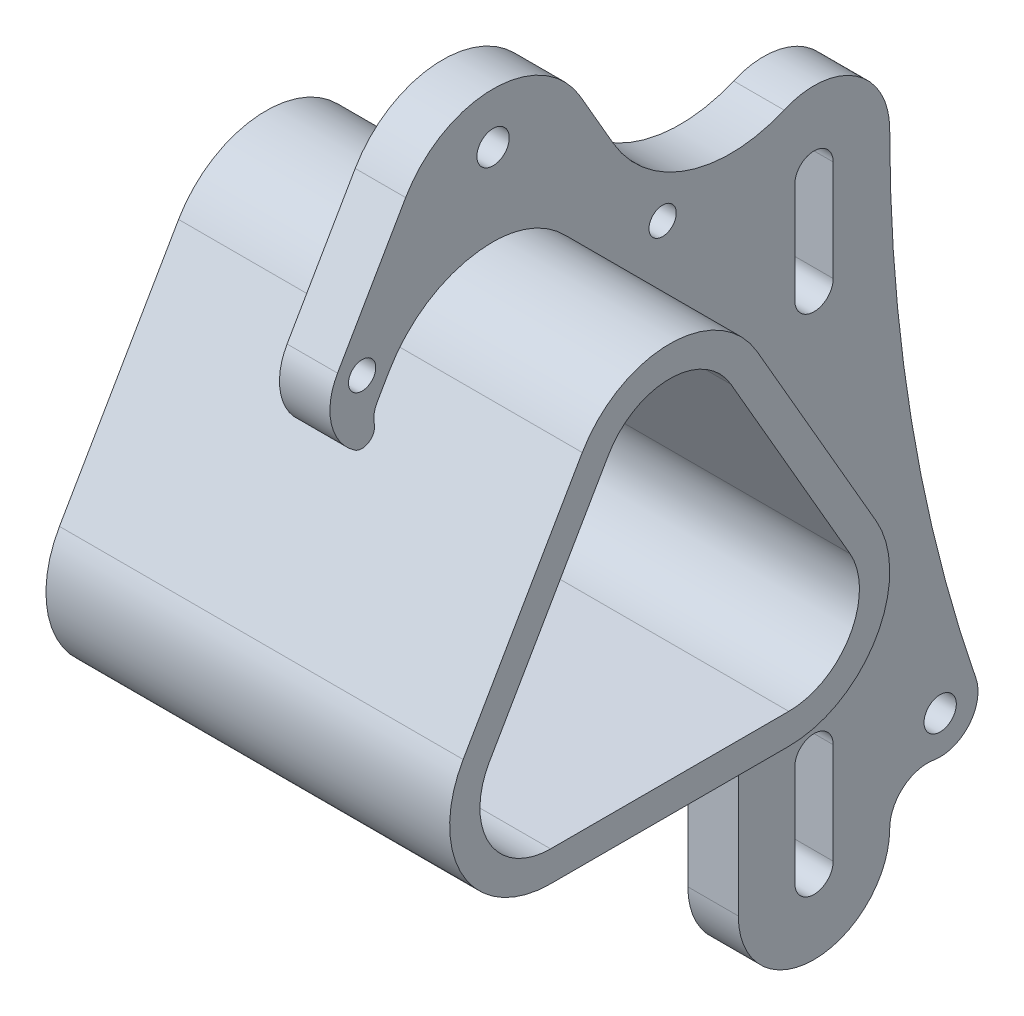
SolidWorks part; units mm, degrees
ref_plane "Front Plane" through (0, 0, 0) normal (0, 0, 1) x (1, 0, 0)
ref_plane "Top Plane" through (0, 0, 0) normal (0, 1, 0) x (1, 0, 0)
ref_plane "Right Plane" through (0, 0, 0) normal (1, 0, 0) x (0, 0, -1)
sketch "Sketch1" plane through (0, 0, 0) normal (1, 0, 0) x (0, 0, -1)
  line L0 (-9.525, 0) -> (-9.525, 48.1449)
  line L1 (-9.525, 48.1449) -> (-29.3888, 82.55)
  line L2 (-14.4015, 56.5912) -> (-29.3888, 82.55)
  line L3 (-51.3858, 82.55) -> (-66.3732, 56.5912)
  line L4 (-55.3746, 37.5412) -> (-25.4, 37.5412)
  line L5 (-55.3746, 41.3512) -> (-25.4, 41.3512)
  line L6 (-48.0863, 80.645) -> (-63.0736, 54.6862)
  line L7 (-17.701, 54.6862) -> (-32.6884, 80.645)
  line L8 (-12.7, 50.2412) -> (-12.7, 3.0715) construction
  line L9 (-51.3858, 82.55) -> (-47.7087, 88.919) construction
  line L10 (-53.4481, 81.3594) -> (-55.7729, 77.3327)
  line L11 (-59.957, 84.373) -> (-51.3858, 99.2188)
  line L12 (-29.3888, 99.2188) -> (-25.2644, 92.075)
  line L13 (-40.3873, 92.8688) -> (-23.8895, 92.8688) construction
  line L14 (-56.8851, 76.2) -> (-40.3873, 76.2) construction
  line L15 (0, 76.2) -> (0, 63.5) construction
  arc A0 (-9.525, 0) -> (9.525, 0) centre (0, 0) ccw
  arc A1 (-29.3888, 82.55) -> (-40.3873, 88.9) centre (-40.3873, 76.2) ccw
  arc A2 (-14.4015, 56.5912) -> (-25.4, 37.5412) centre (-25.4, 50.2412) cw
  arc A3 (-29.3888, 82.55) -> (-51.3858, 82.55) centre (-40.3873, 76.2) ccw
  arc A4 (-66.3732, 56.5912) -> (-55.3746, 37.5412) centre (-55.3746, 50.2412) ccw
  arc A5 (-17.701, 54.6862) -> (-25.4, 41.3512) centre (-25.4, 50.2412) cw
  arc A6 (-63.0736, 54.6862) -> (-55.3746, 41.3512) centre (-55.3746, 50.2412) ccw
  arc A7 (-32.6884, 80.645) -> (-48.0863, 80.645) centre (-40.3873, 76.2) ccw
  arc A8 (-40.3873, 88.9) -> (-51.3858, 82.55) centre (-40.3873, 76.2) ccw construction
  arc A9 (-40.3873, 88.9) -> (-53.4481, 81.3594) centre (-40.3873, 73.8188) ccw
  arc A10 (-55.7729, 77.3327) -> (-57.775, 74.8854) centre (-56.8851, 76.2) cw
  arc A11 (-57.775, 74.8854) -> (-59.957, 84.373) centre (-53.7704, 80.8011) cw
  arc A12 (-51.3858, 99.2188) -> (-29.3888, 99.2188) centre (-40.3873, 92.8688) cw
  arc A13 (-29.3888, 82.55) -> (-51.3858, 82.55) centre (-40.3873, 76.2) ccw construction
  arc A14 (-25.2644, 92.075) -> (-23.8899, 94.4562) centre (-23.8895, 92.8688) ccw construction
  arc A16 (-3.7692, 84.9475) -> (9.525, 76.2) centre (0, 76.2) cw
  arc A17 (9.525, 0) -> (15.0813, 4.6959) centre (14.2875, 0) cw
  arc A18 (15.0813, 4.6959) -> (20.3811, 10.9335) centre (15.875, 9.3918) ccw
  arc A20 (9.525, 76.2) -> (20.3811, 10.9335) centre (211.1439, 76.2) ccw
  arc A21 (-66.3732, 56.5912) -> (-55.3746, 37.5412) centre (-55.3746, 50.2412) ccw construction
  arc A22 (-32.6884, 80.645) -> (-48.0863, 80.645) centre (-40.3873, 76.2) ccw construction
  arc A23 (-25.2644, 92.075) -> (-3.7692, 84.9475) centre (-10.5106, 100.5931) ccw
  point P17 (-40.3873, 88.9)
  point P18 (-40.3873, 37.5412)
  point P45 (-40.3873, 118.2688)
  dimension "D1" = 12.7
  dimension "D6" = 60
  dimension "D7" = 1.1906
  dimension "D8" = 1.5875
  dimension "D9" = 12.7
  dimension "D12" = 9.525
  dimension "D13" = 9.525
  dimension "D15" = 4.7625
  dimension "D17" = 88.9
  dimension "D2" = 51.3588
  dimension "D4" = 3.175
  dimension "D5" = 150
  dimension "D10" = 7.1437
  dimension "D11" = 12.7
  dimension "D14" = 15.875
  dimension "D16" = 63.5
  dimension "D18" = 12.7
  dimension "D3" = 3.81
extrude "Boss-Extrude1" add sketch "Sketch1" along normal mid plane 6.35 contours A23 L12 A12 L11 A11 A10 L10 A9 A1 L1 L0 A0 A17 A18 A20 A16 region at (0, 51.1028, 8.5668)
extrude "Boss-Extrude2" add sketch "Sketch1<3>" along normal mid plane 50.8 separate body contours L3 A4 L4 A2 L1 A1 A3 A7 L7 A5 L5 A6 L6 region at (0, 44.2688, 15.0555)
sketch "Sketch1<3>" plane through (0, 0, 0) normal (1, 0, 0) x (0, 0, -1) same geometry as "Sketch1"
sketch "Sketch2" plane through (3.175, 0, 0) normal (1, 0, 0) x (0, 0, -1)
  line L0 (0, 0) -> (0, 12.7) construction
  line L1 (-2.413, 0) -> (-2.413, 12.7)
  line L2 (2.413, 0) -> (2.413, 12.7)
  line L3 (0, 76.2) -> (0, 63.5) construction
  line L4 (2.413, 76.2) -> (2.413, 63.5)
  line L5 (-2.413, 76.2) -> (-2.413, 63.5)
  circle A4 centre (15.875, 9.3918) radius 2.032
  arc A7 (-2.413, 0) -> (2.413, 0) centre (0, 0) ccw
  arc A8 (2.413, 12.7) -> (-2.413, 12.7) centre (0, 12.7) ccw
  arc A9 (2.413, 76.2) -> (-2.413, 76.2) centre (0, 76.2) ccw
  arc A10 (-2.413, 63.5) -> (2.413, 63.5) centre (0, 63.5) ccw
  point P2 (0, 6.35)
  point P7 (0, 69.85)
  dimension "D2" = 4.826
  dimension "D3" = 4.064
  dimension "D1" = 12.7
extrude "Cut-Extrude1" cut sketch "Sketch2" against normal through all
fillet "Fillet1" radius 3.175 1 edges at (0, 77.3327, 55.7729)
sketch "Sketch3" plane through (3.175, 0, 0) normal (1, 0, 0) x (0, 0, -1)
  line L0 (-9.525, 48.1449) -> (-29.3888, 82.55) construction
  line L1 (-9.525, 0) -> (-9.525, 48.1449) construction
  line L2 (-53.4481, 81.3594) -> (-54.9664, 78.7296) construction
  circle A6 centre (-56.8637, 82.5871) radius 3.5719 construction
  circle A7 centre (-40.3873, 99.2188) radius 6.35 construction
  circle A8 centre (-19.05, 80.5177) radius 3.5719 construction
  arc A9 (-59.957, 84.373) -> (-57.775, 74.8854) centre (-53.7704, 80.8011) ccw construction
  arc A13 (-29.3888, 99.2188) -> (-51.3858, 99.2188) centre (-40.3873, 92.8688) ccw construction
  circle A14 centre (-40.3873, 99.2188) radius 2.032
  circle A15 centre (-19.05, 80.5177) radius 1.7145
  circle A16 centre (-56.8637, 82.5871) radius 1.7145
  point P13 (-23.9109, 69.8871)
  point P23 (-21.1197, 65.0525)
  dimension "D1" = 12.7
  dimension "D2" = 4.064
  dimension "D3" = 3.429
  dimension "D5" = 9.525
  dimension "D4" = 7.9375
extrude "Cut-Extrude2" cut sketch "Sketch3" against normal through all
